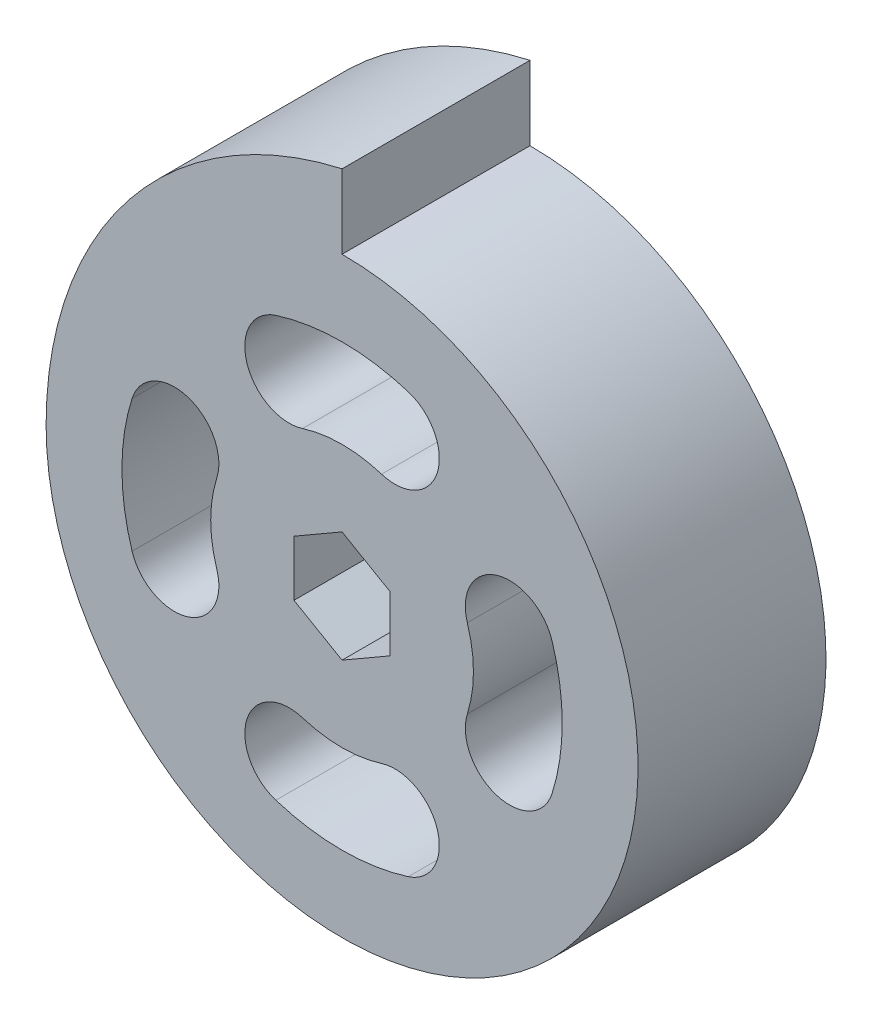
SolidWorks part; units mm, degrees
material "AR500"
ref_plane "Front Plane" through (0, 0, 0) normal (0, 0, 1) x (1, 0, 0)
ref_plane "Top Plane" through (0, 0, 0) normal (0, 1, 0) x (1, 0, 0)
ref_plane "Right Plane" through (0, 0, 0) normal (1, 0, 0) x (0, 0, -1)
sketch "Sketch3" plane through (0, 0, 0) normal (0, 0, 1) x (1, 0, 0)
  line L5 (0, 20) -> (0, 25)
  line L6 (3.25, -1.8764) -> (3.25, 1.8764)
  line L7 (3.25, 1.8764) -> (0, 3.7528)
  line L8 (0, 3.7528) -> (-3.25, 1.8764)
  line L9 (-3.25, 1.8764) -> (-3.25, -1.8764)
  line L10 (-3.25, -1.8764) -> (0, -3.7528)
  line L11 (0, -3.7528) -> (3.25, -1.8764)
  circle A2 centre (0, 0) radius 20 construction
  circle A3 centre (0, 0) radius 3.25 construction
  arc A9 (0, 25) -> (-20, 0) centre (5.625, 0) ccw
  arc A10 (0, 20) -> (-20, 0) centre (0, 0) cw
  point P0 (0.2167, 3.7465)
  point P2 (-18.4747, 7.6605)
  point P3 (0, 0)
  point P13 (0, 0)
  point P17 (0, 0)
  point P25 (0, 0)
  point P26 (0, 16)
  point P27 (0, 16)
  dimension "D2" = 5
  dimension "D1" = 40
  dimension "D3" = 6.5
extrude "Boss-Extrude1" add sketch "Sketch3" along normal blind 12.7
sketch "Sketch4" plane through (0, 0, 12.7) normal (0, 0, 1) x (1, 0, 0)
  line L0 (0, 20) -> (0, 3.7528) construction
  line L1 (-3.5713, 11.3267) -> (0, 0) construction
  line L2 (0, 0) -> (3.5713, 11.3267) construction
  circle A0 centre (0, 0) radius 11.8764 construction
  circle A2 centre (-3.5713, 11.3267) radius 3 construction
  circle A3 centre (3.5713, 11.3267) radius 3 construction
  arc A4 (-4.4734, 14.1879) -> (4.4734, 14.1879) centre (0, 0) cw
  arc A5 (2.6692, 8.4656) -> (-2.6692, 8.4656) centre (0, 0) ccw
  circle A6 centre (0, 11.8764) radius 3 construction
  arc A7 (-4.4734, 14.1879) -> (-2.6692, 8.4656) centre (-3.5713, 11.3267) ccw
  arc A8 (2.6692, 8.4656) -> (4.4734, 14.1879) centre (3.5713, 11.3267) ccw
  point P5 (0, 11.8764)
  point P7 (0, 20)
  dimension "D2" = 3
  dimension "D1" = 35
extrude "Cut-Extrude1" cut sketch "Sketch4" against normal through all
ref_axis "Axis1" through (0, 0, -0.475) along (0, 0, 1)
pattern_circular "CirPattern1" count 4 over 360 about axis through (0, 0, -0.475) along (0, 0, 1) of "Cut-Extrude1"
